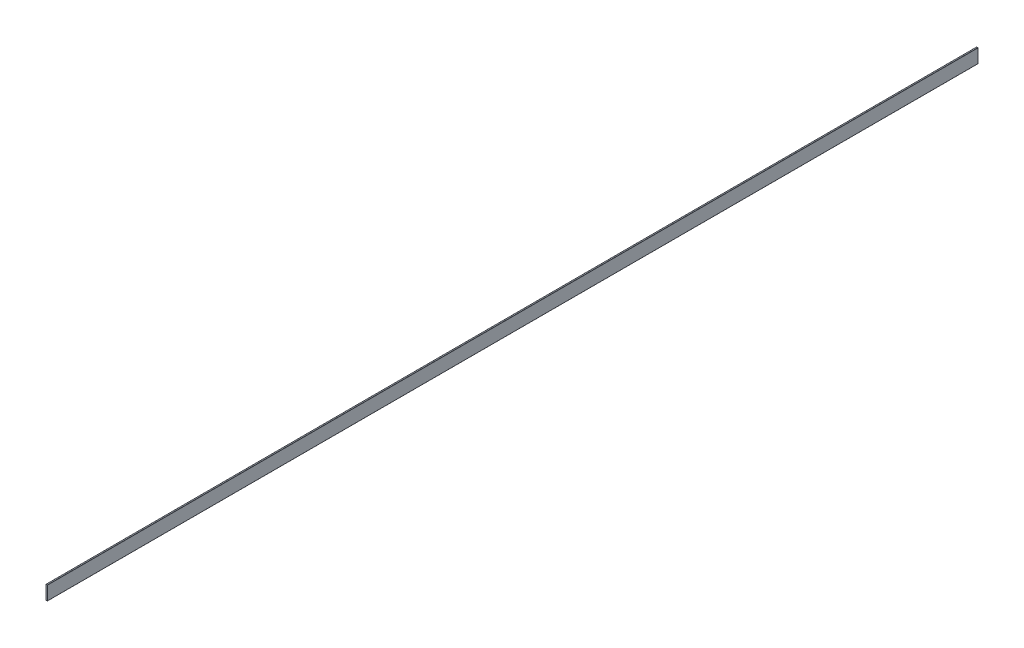
SolidWorks part; units mm, degrees
material "Alloy Steel"
ref_plane "Front Plane" through (0, 0, 0) normal (0, 0, 1) x (1, 0, 0)
ref_plane "Top Plane" through (0, 0, 0) normal (0, 1, 0) x (1, 0, 0)
ref_plane "Right Plane" through (0, 0, 0) normal (1, 0, 0) x (0, 0, -1)
sketch "Sketch1" plane through (0, 0, 0) normal (0, 0, 1) x (1, 0, 0)
  line L1 (-1.15, -15) -> (1.15, -15)
  line L2 (-1.5, -14.65) -> (-1.5, 14.65)
  line L3 (-1.15, 15) -> (1.15, 15)
  line L4 (1.5, -14.65) -> (1.5, 14.65)
  line L5 (-1.5, -15) -> (1.5, 15) construction
  line L6 (-1.5, 15) -> (1.5, -15) construction
  arc A0 (-1.15, -15) -> (-1.5, -14.65) centre (-1.15, -14.65) cw
  arc A1 (1.15, -15) -> (1.5, -14.65) centre (1.15, -14.65) ccw
  arc A2 (1.15, 15) -> (1.5, 14.65) centre (1.15, 14.65) cw
  arc A3 (-1.5, 14.65) -> (-1.15, 15) centre (-1.15, 14.65) cw
  point P0 (0, 0)
  dimension "D3" = 0.35
  dimension "D1" = 30
  dimension "D2" = 3
extrude "Boss-Extrude1" add sketch "Sketch1" along normal blind 1000 and the other way blind 1000
